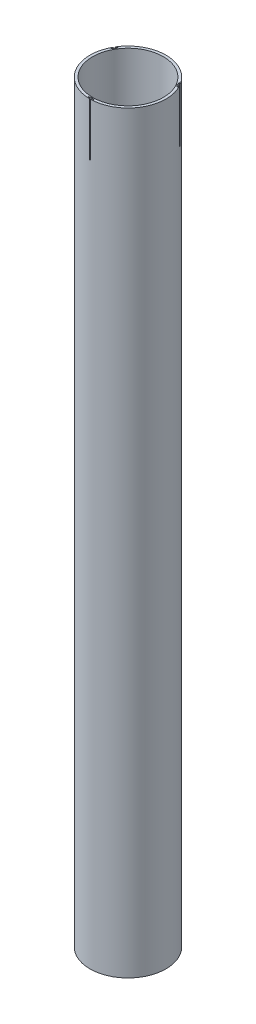
SolidWorks part; units mm, degrees
ref_plane "Front Plane" through (0, 0, 0) normal (0, 0, 1) x (1, 0, 0)
ref_plane "Top Plane" through (0, 0, 0) normal (0, 1, 0) x (1, 0, 0)
ref_plane "Right Plane" through (0, 0, 0) normal (1, 0, 0) x (0, 0, -1)
sketch "Sketch1" plane through (0, 0, 0) normal (0, 1, 0) x (1, 0, 0)
  circle A0 centre (0, 0) radius 57.5
  dimension "D1" = 115
extrude "Boss-Extrude1" add sketch "Sketch1" along normal mid plane 1140
ref_plane "Plane1" through (0, 490, 0) normal (0, 1, 0) x (1, 0, 0)
ref_plane "Plane2" through (0, 570, 0) normal (0, 1, 0) x (1, 0, 0)
shell "Shell1" thickness 4 removed face at (0, 570, 57.5) removed face at (0, -570, 57.5)
sketch "Sketch2" plane through (0, 570, 0) normal (0, 1, 0) x (1, 0, 0)
  line L0 (0, 64.7023) -> (0, -68.4384) construction
  line L1 (1, -57.4913) -> (1, -56.5087)
  line L13 (4, -56.5087) -> (4, -55.5087)
  line L14 (1, -56.5087) -> (4, -56.5087)
  line L15 (4, -55.5087) -> (0, -54.5087)
  line L16 (-4, -55.5087) -> (0, -54.5087)
  line L17 (-4, -56.5087) -> (-4, -55.5087)
  line L18 (-1, -56.5087) -> (-4, -56.5087)
  line L19 (-1, -57.4913) -> (-1, -56.5087)
  arc A0 (-1, -57.4913) -> (1, -57.4913) centre (0, 0) ccw
  circle A1 centre (0, 0) radius 57.5 construction
extrude "Cut-Extrude4" cut sketch "Sketch2" against normal blind 80
ref_axis "Axis1" through (0, -777.4745, 0) along (0, 1, 0)
pattern_circular "CirPattern1" count 3 over 360 about axis through (0, -777.4745, 0) along (0, 1, 0) of "Cut-Extrude4"
ref_plane "Plane3" through (0, -570, 0) normal (0, -1, 0) x (-1, 0, 0)
sketch "Sketch3" plane through (0, -570, 0) normal (0, -1, 0) x (-1, 0, 0)
  line L0 (4.4821, 53.3119) -> (0, 0) construction
  line L1 (4.4821, 53.3119) -> (2.1363, 25.4104)
  line L2 (-22.7744, 48.4105) -> (0, 0) construction
  line L3 (-22.7744, 48.4105) -> (-10.8534, 23.0706)
  circle A0 centre (0, 0) radius 53.5 construction
  circle A1 centre (0, 0) radius 25.5 construction
  arc A2 (4.4821, 53.3119) -> (-22.7744, 48.4105) centre (0, 0) ccw
  arc A3 (2.1363, 25.4104) -> (-10.8551, 23.0742) centre (0, 0) ccw
sketch "Sketch4" plane through (0, -570, 0) normal (0, -1, 0) x (-1, 0, 0)
  line L0 (0, 0) -> (4.4821, 53.3119) construction
  line L1 (4.4821, 53.3119) -> (2.1363, 25.4104)
  line L2 (-10.8551, 23.0742) -> (-22.7744, 48.4105)
  line L3 (-4.4821, -53.3119) -> (4.4821, 53.3119) construction
  line L4 (-4.4821, -53.3119) -> (-2.1363, -25.4104)
  line L5 (22.7744, -48.4105) -> (-22.7744, 48.4105) construction
  line L6 (10.8551, -23.0742) -> (22.7744, -48.4105)
  arc A0 (4.4821, 53.3119) -> (-22.7744, 48.4105) centre (0, 0) ccw
  arc A1 (2.1363, 25.4104) -> (-10.8551, 23.0742) centre (0, 0) ccw
  arc A2 (-2.1363, -25.4104) -> (10.8551, -23.0742) centre (0, 0) ccw
  arc A3 (-4.4821, -53.3119) -> (22.7744, -48.4105) centre (0, 0) ccw
  point P11 (0, 0)
  point P14 (0, 0)
extrude "Boss-Extrude3" add sketch "Sketch4" against normal blind 5
